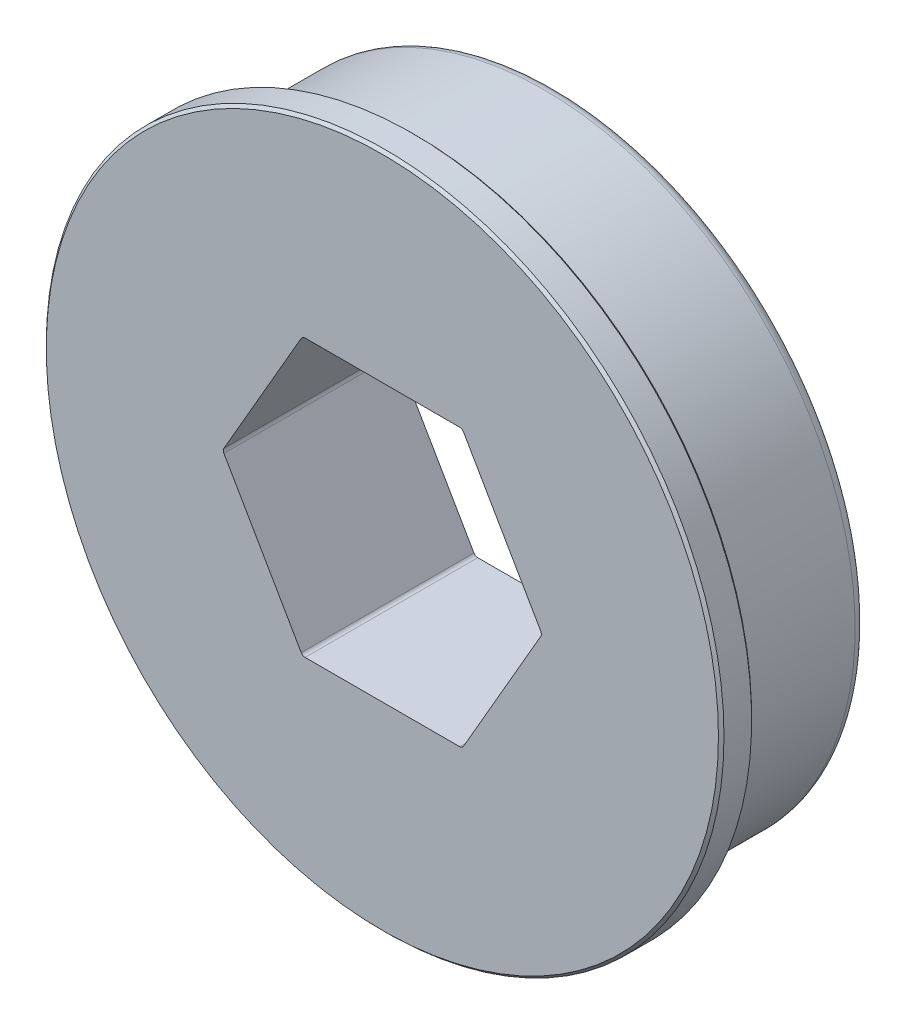
SolidWorks part; units mm, degrees
material "AISI 1020"
ref_plane "Front Plane" through (0, 0, 0) normal (0, 0, 1) x (1, 0, 0)
ref_plane "Top Plane" through (0, 0, 0) normal (0, 1, 0) x (1, 0, 0)
ref_plane "Right Plane" through (0, 0, 0) normal (1, 0, 0) x (0, 0, -1)
ref_plane "Plane1" through (0, 0, 0) normal (0, -1, 0) x (1, 0, 0)
sketch "Sketch1" plane through (0, 0, 0) normal (0, -1, 0) x (1, 0, 0)
  line L0 (15.5575, 7.9273) -> (0, 7.9273)
  line L1 (0, 7.9273) -> (0, 0)
  line L2 (0, 0) -> (14.2875, 0)
  line L3 (14.2875, 0) -> (14.2875, 5.8953)
  line L4 (14.2875, 5.8953) -> (13.97, 5.8953)
  line L5 (13.97, 5.8953) -> (13.97, 6.4033)
  line L6 (13.97, 6.4033) -> (15.5575, 6.4033)
  line L7 (15.5575, 6.4033) -> (15.5575, 7.9273)
  line L8 (0, 7.9273) -> (0, 0) construction
revolve "Revolve1" add sketch "Sketch1" angle 360 about L8 reverse direction yes
sketch "Sketch2" plane through (0, 0, 0) normal (0, 0, -1) x (-1, 0, 0)
  line L0 (3.6662, 6.35) -> (-3.6662, 6.35)
  line L1 (-3.6662, 6.35) -> (-7.3323, 0)
  line L2 (-7.3323, 0) -> (-3.6662, -6.35)
  line L3 (-3.6662, -6.35) -> (3.6662, -6.35)
  line L4 (3.6662, -6.35) -> (7.3323, 0)
  line L5 (7.3323, 0) -> (3.6662, 6.35)
extrude "Cut-Extrude1" cut sketch "Sketch2" against normal through all
chamfer "Chamfer1" distance 0.127 angle 45 2 edges at (-15.5575, 0, 7.9273) (-15.5575, 0, 6.4033)
fillet "Fillet1" radius 0.2032 6 edges at (-3.6662, -6.35, 3.9637) (7.3323, 0, 3.9637) (-7.3323, 0, 3.9637) (-3.6662, 6.35, 3.9637) (3.6662, -6.35, 3.9637) (3.6662, 6.35, 3.9637) tangent propagation no
fillet "Fillet2" radius 0.508 1 edges at (-14.2875, 0, 0) tangent propagation no
